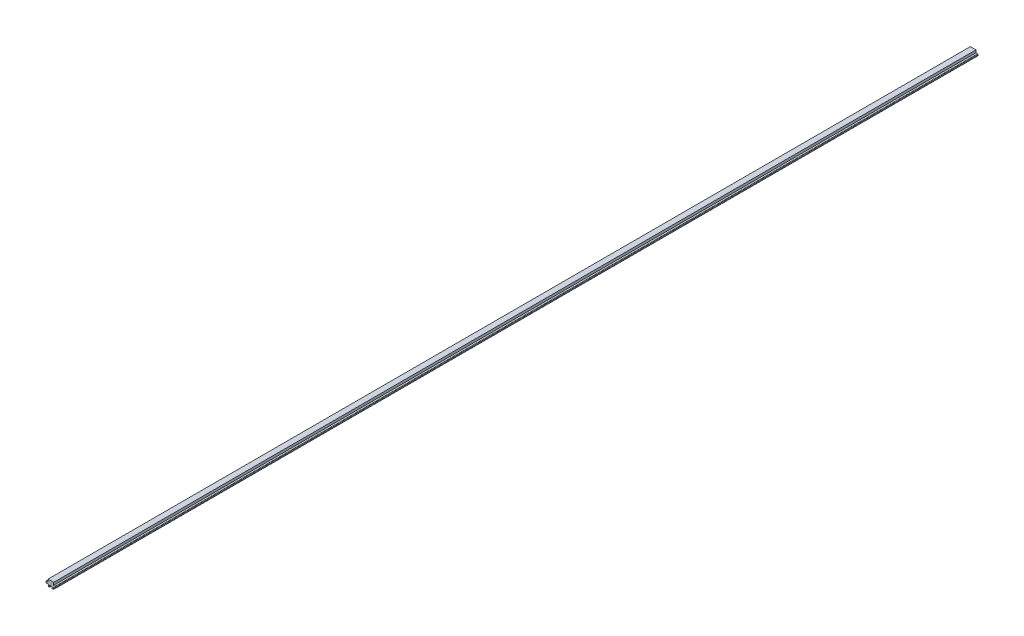
SolidWorks part; units mm, degrees
ref_plane "Front Plane" through (0, 0, 0) normal (0, 0, 1) x (1, 0, 0)
ref_plane "Top Plane" through (0, 0, 0) normal (0, 1, 0) x (1, 0, 0)
ref_plane "Right Plane" through (0, 0, 0) normal (1, 0, 0) x (0, 0, -1)
sketch "Sketch2" plane through (0, 0, 0) normal (0, 0, 1) x (1, 0, 0)
  line L0 (-1.4166, 5.1268) -> (-1.4166, -5.0982) construction
  line L5 (-4.4666, 2.8768) -> (1.6334, 2.8768)
  line L6 (-4.4666, 2.8768) -> (-4.4666, -1.8732)
  line L7 (-4.4666, -1.8732) -> (1.6334, -1.8732)
  line L8 (1.6334, 2.8768) -> (1.6334, -1.8732)
  line L9 (1.6334, 0.1268) -> (3.8334, 0.1268)
  line L10 (1.6334, 0.1268) -> (1.6334, -1.8732)
  line L11 (1.6334, -1.8732) -> (3.8334, -1.8732)
  line L12 (3.8334, 0.1268) -> (3.8334, -1.8732)
  line L13 (-4.4666, -1.8732) -> (-6.6666, -1.8732)
  line L14 (-0.1166, -1.8732) -> (1.3834, -1.8732)
  line L15 (-0.1166, -1.8732) -> (-0.1166, -4.0732)
  line L16 (-0.1166, -4.0732) -> (1.3834, -4.0732)
  line L17 (1.3834, -1.8732) -> (1.3834, -4.0732)
  line L18 (-6.6666, 0.1268) -> (-6.6666, -1.8732)
  line L19 (-4.4666, 0.1268) -> (-6.6666, 0.1268)
  line L20 (-4.4666, 0.1268) -> (-4.4666, -1.8732)
  line L21 (-2.7166, -4.0732) -> (-4.2166, -4.0732)
  line L22 (-4.2166, -1.8732) -> (-4.2166, -4.0732)
  line L23 (-2.7166, -1.8732) -> (-4.2166, -1.8732)
  line L24 (-2.7166, -1.8732) -> (-2.7166, -4.0732)
  dimension "D1" = 6.1
  dimension "D4" = 2.2
  dimension "D5" = 2
  dimension "D6" = 1.3
  dimension "D7" = 2.2
  dimension "D8" = 1.5
  dimension "D9" = 4.4666
extrude "Boss-Extrude1" add sketch "Sketch2" along normal blind 1000 contours L0 L5 | L0 L6 L7 | L5 L0 L7 L8 | L0 | L12 L9 L8 L11 | L17 L7 L15 L16 | L24 L7 L22 L21 | L6 L19 L18 L13 region at (0.1084, 0.5018, 0) region at (-2.9416, 0.5018, 0) region at (-3.4666, -2.9732, 0) region at (0.6334, -2.9732, 0) region at (-5.5666, -0.8732, 0) region at (2.7334, -0.8732, 0)
fillet "Fillet1" radius 0.5 4 edges at (3.8334, -1.8732, 500) (3.8334, 0.1268, 500) (-6.6666, -1.8732, 500) (-6.6666, 0.1268, 500)
fillet "Fillet2" radius 0.5 4 edges at (1.3834, -4.0732, 500) (-0.1166, -4.0732, 500) (-4.2166, -4.0732, 500) (-2.7166, -4.0732, 500)
